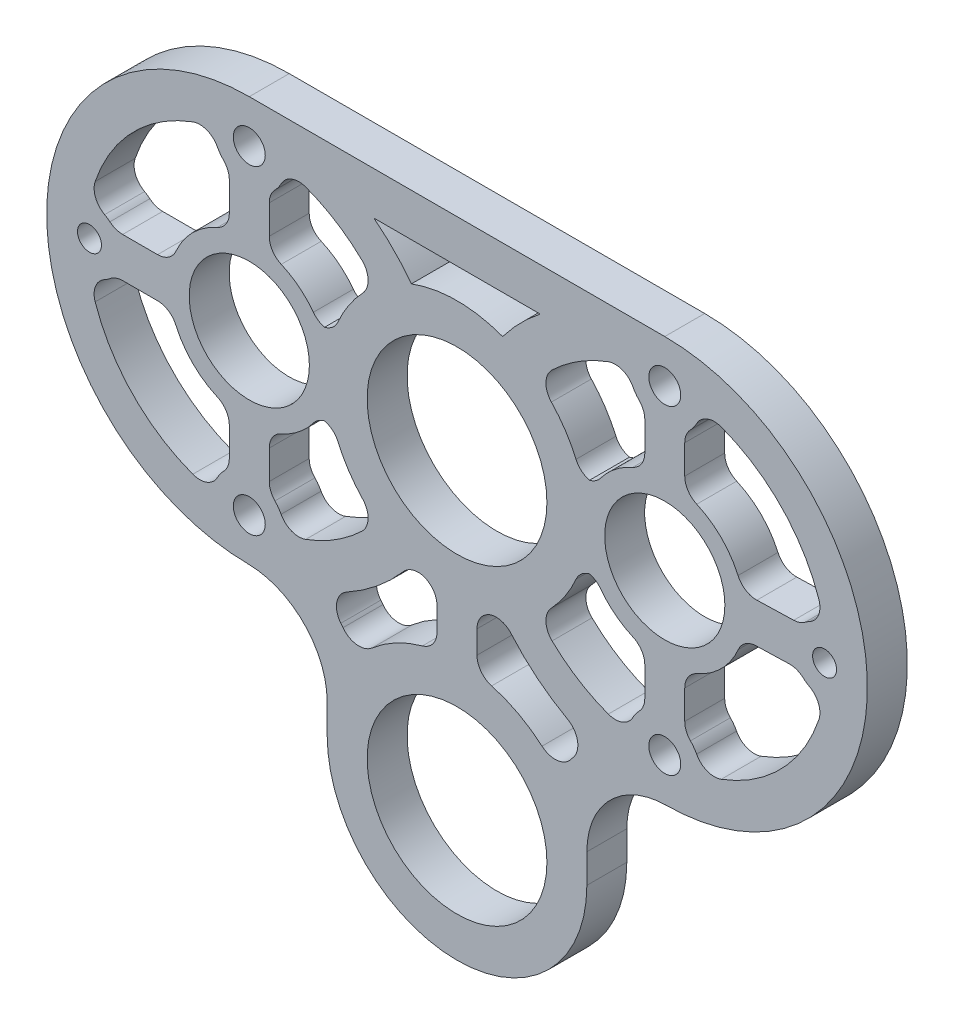
SolidWorks part; units mm, degrees
material "6061 Alloy"
ref_plane "Front Plane" through (0, 0, 0) normal (0, 0, 1) x (1, 0, 0)
ref_plane "Top Plane" through (0, 0, 0) normal (0, 1, 0) x (1, 0, 0)
ref_plane "Right Plane" through (0, 0, 0) normal (1, 0, 0) x (0, 0, -1)
sketch "Sketch1" plane through (0, 0, 0) normal (0, 0, 1) x (1, 0, 0)
  line L0 (-45.3751, -115.4114) -> (-45.3751, -110.7886)
  line L1 (-70.0805, -62.7064) -> (-79.192, -62.7064)
  line L2 (-60.9326, -45.2333) -> (-60.9326, -53.5585)
  line L3 (-60.9326, -86.5295) -> (-60.9326, -78.2044)
  line L4 (-54.5826, -45.2333) -> (-54.5826, -53.5585)
  line L5 (-46.7298, -59.5314) -> (-44.3739, -59.5314)
  line L6 (-54.5826, -86.5295) -> (-54.5826, -78.2044)
  line L7 (-70.0805, -69.0564) -> (-79.192, -69.0564)
  line L8 (-58.0751, -98.0886) -> (-57.7576, -98.0886)
  line L9 (-46.7298, -72.2314) -> (-44.3739, -72.2314)
  line L10 (-24.7376, -4.929) -> (-24.7376, -7.3556)
  line L11 (-4.1001, -115.4114) -> (-4.1001, -110.7886)
  line L12 (8.5999, -98.0886) -> (8.2824, -98.0886)
  line L13 (-27.9126, -86.2732) -> (-27.9126, -95.0196)
  line L14 (-21.5626, -86.2732) -> (-21.5626, -95.0196)
  line L16 (-57.7576, -33.6742) -> (8.2824, -33.6742)
  line L17 (-11.5202, -40.4814) -> (-37.955, -40.4814)
  line L19 (-2.7454, -72.2314) -> (-5.1013, -72.2314)
  line L21 (20.6054, -69.0564) -> (29.5228, -68.7976)
  line L22 (5.1074, -86.5295) -> (5.1074, -78.2044)
  line L23 (-2.7454, -59.5314) -> (-5.1013, -59.5314)
  line L24 (5.1074, -45.2333) -> (5.1074, -53.5585)
  line L25 (11.4574, -86.5295) -> (11.4574, -78.2044)
  line L26 (11.4574, -45.2333) -> (11.4574, -53.5585)
  line L27 (20.6054, -62.7064) -> (29.9387, -62.4476)
  circle A0 centre (-57.7576, -65.8814) radius 9.5504
  circle A1 centre (-57.7576, -40.4814) radius 2.54
  circle A2 centre (-24.7376, -115.4114) radius 14.2875
  circle A3 centre (-57.7576, -91.2814) radius 2.54
  arc A4 (-45.3751, -115.4114) -> (-4.1001, -115.4114) centre (-24.7376, -115.4114) ccw
  arc A5 (-52.0455, -91.0998) -> (-54.5826, -86.5295) centre (-57.7576, -91.2814) ccw
  arc A6 (-52.0455, -91.0998) -> (-37.5727, -82.042) centre (-57.7576, -65.8814) ccw
  arc A7 (-52.0455, -40.663) -> (-54.5826, -45.2333) centre (-57.7576, -40.4814) cw
  arc A8 (-60.9326, -45.2333) -> (-63.4697, -40.663) centre (-57.7576, -40.4814) cw
  arc A9 (-54.5826, -78.2044) -> (-46.7298, -72.2314) centre (-57.7576, -65.8814) ccw
  arc A10 (-60.9326, -86.5295) -> (-63.4697, -91.0998) centre (-57.7576, -91.2814) ccw
  arc A11 (-83.1109, -70.9612) -> (-63.4697, -91.0998) centre (-57.7576, -65.8814) ccw
  arc A12 (-60.9326, -53.5585) -> (-70.0805, -62.7064) centre (-57.7576, -65.8814) ccw
  arc A13 (-45.3751, -110.7886) -> (-58.0751, -98.0886) centre (-58.0751, -110.7886) ccw
  arc A14 (-70.0805, -69.0564) -> (-60.9326, -78.2044) centre (-57.7576, -65.8814) ccw
  arc A15 (-46.7298, -59.5314) -> (-54.5826, -53.5585) centre (-57.7576, -65.8814) ccw
  arc A16 (-63.4697, -40.663) -> (-83.1109, -60.8016) centre (-57.7576, -65.8814) ccw
  arc A17 (8.5999, -98.0886) -> (-4.1001, -110.7886) centre (8.5999, -110.7886) ccw
  arc A18 (-46.1573, -95.927) -> (-31.9896, -85.2028) centre (-57.7576, -65.8814) ccw
  arc A19 (-31.9896, -85.2028) -> (-27.9126, -86.2732) centre (-24.7376, -65.8814) ccw
  circle A20 centre (-24.7376, -65.8814) radius 14.2875
  arc A21 (-37.5727, -49.7208) -> (-44.3739, -59.5314) centre (-24.7376, -65.8814) ccw
  arc A22 (-37.5727, -49.7208) -> (-52.0455, -40.663) centre (-57.7576, -65.8814) ccw
  arc A23 (-44.3739, -72.2314) -> (-37.5727, -82.042) centre (-24.7376, -65.8814) ccw
  arc A24 (-31.9896, -46.5601) -> (-37.955, -40.4814) centre (-57.7576, -65.8814) ccw
  arc A25 (-17.4856, -46.5601) -> (-31.9896, -46.5601) centre (-24.7376, -65.8814) ccw
  arc A26 (-40.8907, -102.5668) -> (-46.1573, -95.927) centre (-58.0751, -110.7886) ccw
  arc A27 (-17.4233, -85.1793) -> (-3.2601, -95.8808) centre (8.2824, -65.8814) ccw
  arc A28 (-57.7576, -33.6742) -> (-57.7576, -98.0886) centre (-57.7576, -65.8814) ccw
  arc A29 (-8.5845, -102.5668) -> (-3.2601, -95.8808) centre (8.5999, -110.7886) cw
  arc A30 (-8.5845, -102.5668) -> (-21.5626, -95.0196) centre (-24.7376, -115.4114) ccw
  arc A31 (-21.5626, -86.2732) -> (-17.4233, -85.1793) centre (-24.7376, -65.8814) ccw
  arc A32 (-27.9126, -95.0196) -> (-40.8907, -102.5668) centre (-24.7376, -115.4114) ccw
  circle A33 centre (-83.1576, -65.8814) radius 1.905
  arc A34 (8.2824, -33.6742) -> (8.2824, -98.0886) centre (8.2824, -65.8814) cw
  arc A35 (-79.192, -62.7064) -> (-83.1109, -60.8016) centre (-83.1576, -65.8814) ccw
  arc A36 (-83.1109, -70.9612) -> (-79.192, -69.0564) centre (-83.1576, -65.8814) ccw
  arc A37 (-17.4856, -46.5601) -> (-11.5202, -40.4814) centre (8.2824, -65.8814) cw
  arc A38 (-5.1013, -72.2314) -> (-11.9025, -82.042) centre (-24.7376, -65.8814) cw
  arc A39 (-11.9025, -49.7208) -> (2.5703, -40.663) centre (8.2824, -65.8814) cw
  arc A40 (-11.9025, -49.7208) -> (-5.1013, -59.5314) centre (-24.7376, -65.8814) cw
  circle A41 centre (33.6824, -65.8814) radius 1.905
  arc A42 (13.9945, -40.663) -> (33.6357, -60.8016) centre (8.2824, -65.8814) cw
  arc A43 (-2.7454, -59.5314) -> (5.1074, -53.5585) centre (8.2824, -65.8814) cw
  arc A44 (20.6054, -69.0564) -> (11.4574, -78.2044) centre (8.2824, -65.8814) cw
  arc A45 (33.6357, -60.8016) -> (29.9387, -62.4476) centre (33.6824, -65.8814) ccw
  arc A46 (11.4574, -53.5585) -> (20.6054, -62.7064) centre (8.2824, -65.8814) cw
  arc A47 (33.6357, -70.9612) -> (13.9945, -91.0998) centre (8.2824, -65.8814) cw
  arc A48 (11.4574, -86.5295) -> (13.9945, -91.0998) centre (8.2824, -91.2814) cw
  arc A49 (5.1074, -78.2044) -> (-2.7454, -72.2314) centre (8.2824, -65.8814) cw
  arc A50 (29.5228, -68.7976) -> (33.6357, -70.9612) centre (33.6824, -65.8814) ccw
  arc A51 (11.4574, -45.2333) -> (13.9945, -40.663) centre (8.2824, -40.4814) ccw
  arc A52 (2.5703, -40.663) -> (5.1074, -45.2333) centre (8.2824, -40.4814) ccw
  arc A53 (2.5703, -91.0998) -> (-11.9025, -82.042) centre (8.2824, -65.8814) cw
  arc A54 (2.5703, -91.0998) -> (5.1074, -86.5295) centre (8.2824, -91.2814) cw
  circle A59 centre (8.2824, -91.2814) radius 2.54
  circle A62 centre (8.2824, -40.4814) radius 2.54
  circle A63 centre (8.2824, -65.8814) radius 9.5504
  point P3 (-24.7376, -65.8814)
  point P19 (-45.3751, -115.4114)
  point P32 (-24.7376, -33.6742)
  point P118 (-45.5518, -59.5314)
  point P121 (-24.7376, -40.4814)
  dimension "D1" = 28.575
  dimension "D2" = 19.1008
  dimension "D4" = 33.02
  dimension "D8" = 25.4
  dimension "D9" = 12.7254
  dimension "D10" = 25.8572
  dimension "D11" = 25.8572
  dimension "D12" = 32.2072
  dimension "D13" = 49.53
  dimension "D14" = 28.575
  dimension "D15" = 6.35
  dimension "D17" = 25.4
  dimension "D18" = 5.08
  dimension "D23" = 25.4
  dimension "D27" = 3.175
  dimension "D7" = 3.175
  dimension "D28" = 6.35
  dimension "D29" = 3.175
  dimension "D30" = 12.7
  dimension "D5" = 33.02
  dimension "D16" = 33.02
  dimension "D24" = 6.35
  dimension "D25" = 3.175
  dimension "D26" = 6.35
  dimension "D36" = 6.35
  dimension "D37" = 0.3175
  dimension "D40" = 3.175
  dimension "D46" = 3.81
  dimension "D41" = 25.4
  dimension "D42" = 3.81
  dimension "D6" = 5.08
  dimension "D19" = 3.175
  dimension "D20" = 12.7
  dimension "D21" = 12.7
  dimension "D22" = 6.35
  dimension "D32" = 6.35
  dimension "D34" = 19.5072
  dimension "D35" = 6.35
  dimension "D44" = 3.175
  dimension "D47" = 3.175
  dimension "D33" = 6.35
  dimension "D38" = 6.35
  dimension "D43" = 3.175
  dimension "D45" = 25.4
  dimension "D31" = 6.35
  dimension "D39" = 6.35
  dimension "D48" = 6.35
extrude "Boss-Extrude1" add sketch "Sketch1" along normal blind 6.35 contours A0 region at (-43.7168, -113.1, 0)
fillet "Fillet1" radius 3.175 48 edges at (-63.4697, -40.663, 3.175) (-60.9326, -45.2333, 3.175) (-60.9326, -53.5585, 3.175) (-70.0805, -62.7064, 3.175) (-5.1013, -59.5314, 3.175) (-2.7454, -59.5314, 3.175) (-2.7454, -72.2314, 3.175) (-5.1013, -72.2314, 3.175) (-11.9025, -82.042, 3.175) (5.1074, -78.2044, 3.175) (2.5703, -91.0998, 3.175) (5.1074, -86.5295, 3.175) (13.9945, -91.0998, 3.175) (11.4574, -86.5295, 3.175) (11.4574, -78.2044, 3.175) (20.6054, -69.0564, 3.175) (11.4574, -53.5585, 3.175) (20.6054, -62.7064, 3.175) (13.9945, -40.663, 3.175) (11.4574, -45.2333, 3.175) (5.1074, -53.5585, 3.175) (5.1074, -45.2333, 3.175) (2.5703, -40.663, 3.175) (-11.9025, -49.7208, 3.175) (-44.3739, -59.5314, 3.175) (-46.7298, -59.5314, 3.175) (-46.7298, -72.2314, 3.175) (-44.3739, -72.2314, 3.175) (-37.5727, -82.042, 3.175) (-52.0455, -91.0998, 3.175) (-54.5826, -86.5295, 3.175) (-54.5826, -78.2044, 3.175) (-63.4697, -91.0998, 3.175) (-60.9326, -86.5295, 3.175) (-60.9326, -78.2044, 3.175) (-70.0805, -69.0564, 3.175) (-37.5727, -49.7208, 3.175) (-54.5826, -53.5585, 3.175) (-54.5826, -45.2333, 3.175) (-52.0455, -40.663, 3.175) (33.6357, -70.9612, 3.175) (29.5228, -68.7976, 3.175) (29.9387, -62.4476, 3.175) (33.6357, -60.8016, 3.175) (-83.1109, -70.9612, 3.175) (-79.192, -69.0564, 3.175) (-83.1109, -60.8016, 3.175) (-79.192, -62.7064, 3.175)
fillet "Fillet2" radius 3.175 10 edges at (-46.1573, -95.927, 3.175) (-40.8907, -102.5668, 3.175) (-27.9126, -95.0196, 3.175) (-8.5845, -102.5668, 3.175) (-3.2601, -95.8808, 3.175) (-21.5626, -95.0196, 3.175) (-17.4233, -85.1793, 3.175) (-21.5626, -86.2732, 3.175) (-27.9126, -86.2732, 3.175) (-31.9896, -85.2028, 3.175)
